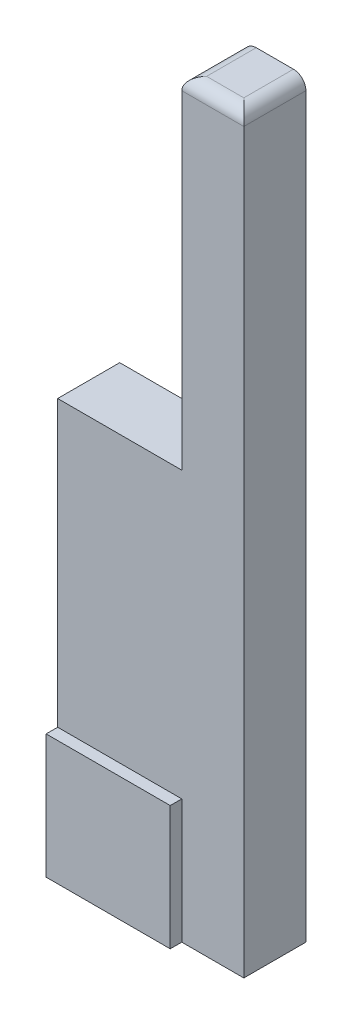
SolidWorks part; units mm, degrees
ref_plane "Front Plane" through (0, 0, 0) normal (0, 0, 1) x (1, 0, 0)
ref_plane "Top Plane" through (0, 0, 0) normal (0, 1, 0) x (1, 0, 0)
ref_plane "Right Plane" through (0, 0, 0) normal (1, 0, 0) x (0, 0, -1)
sketch "Sketch1" plane through (0, 0, 0) normal (0, 0, 1) x (1, 0, 0)
  line L0 (73.1733, 0) -> (-83.3727, 0) construction
  line L1 (10, 12) -> (10, -15.48)
  line L2 (0, 0) -> (10, 0) construction
  line L3 (0, 0) -> (0, -15.48) construction
  line L4 (0, -15.48) -> (10, -15.48) construction
  line L5 (10, 0) -> (10, -15.48) construction
  line L6 (10, -15.48) -> (0, -15.48)
  line L7 (0, -15.48) -> (0, -48.42)
  line L8 (0, -48.42) -> (15, -48.42)
  line L9 (-83.3727, -7.64) -> (73.1733, -7.64) construction
  line L10 (-83.3727, -48.42) -> (73.1733, -48.42) construction
  line L11 (15, -48.42) -> (15, 12)
  line L12 (15, 12) -> (10, 12)
  line L13 (0, -43.42) -> (15, -43.42) construction
  dimension "D1" = 10
  dimension "D2" = 15.48
  dimension "D3" = 5
  dimension "D4" = 12
  dimension "D5" = 7.64
  dimension "D6" = 40.78
  dimension "D7" = 0
  dimension "D8" = 5
extrude "Boss-Extrude1" add sketch "Sketch1" along normal blind 5
sketch "Sketch2" plane through (0, 0, 0) normal (0, 0, -1) x (-1, 0, 0)
  line L0 (0, -43.42) -> (-10, -43.42) construction
  line L1 (0, -38.42) -> (-10, -38.42)
  line L2 (0, -38.42) -> (0, -48.42)
  line L3 (0, -48.42) -> (-10, -48.42)
  line L4 (-10, -38.42) -> (-10, -48.42)
  line L5 (0, -48.42) -> (-15, -48.42) construction
  line L6 (-10, -15.48) -> (0, -15.48) construction
  line L7 (-5, -31.4048) -> (-5, -38.42) construction
  line L8 (0, -15.48) -> (0, -48.42) construction
  point P10 (-5, -15.48)
  point P13 (-5, -38.42)
  dimension "D1" = 5
  dimension "D2" = 10
  dimension "D3" = 10
extrude "Boss-Extrude2" add sketch "Sketch2" against normal blind 5.93
fillet "Fillet1" radius 1 3 edges at (10, 12, 2.5) (15, 12, 2.5) (12.5, 12, 5)
sketch "Sketch3" plane through (0, -48.42, 0) normal (0, -1, 0) x (1, 0, 0)
  line L0 (15, 2.5) -> (0, 2.5) construction
  line L1 (15, 5) -> (15, 0) construction
  circle A0 centre (12.5, 2.5) radius 1.0294
  dimension "D1" = 2.5
extrude "Cut-Extrude1" cut sketch "Sketch3" against normal blind 0.5
